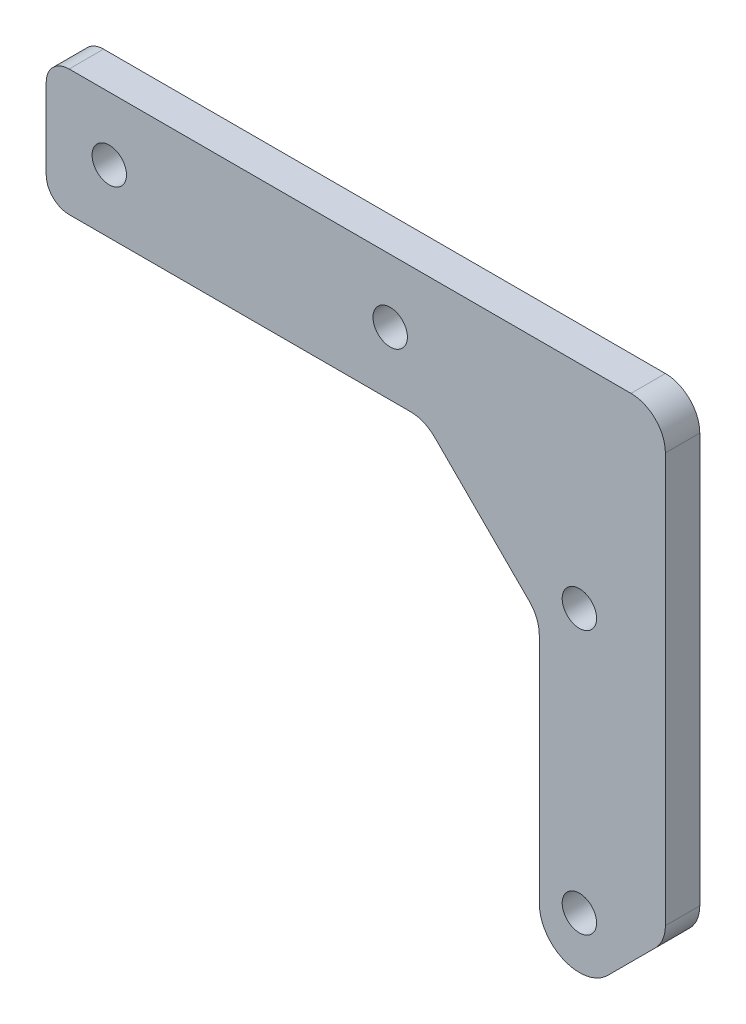
SolidWorks part; units mm, degrees
ref_plane "Спереди" through (0, 0, 0) normal (0, 0, 1) x (1, 0, 0)
ref_plane "Сверху" through (0, 0, 0) normal (0, 1, 0) x (1, 0, 0)
ref_plane "Справа" through (0, 0, 0) normal (1, 0, 0) x (0, 0, -1)
sketch "Эскиз1" plane through (0, 0, 0) normal (0, 0, 1) x (1, 0, 0)
  line L0 (-48.5, 0) -> (5.5, 0) construction
  line L1 (-2, 5.5) -> (-2, -46.5) construction
  line L2 (-48.5, 5.5) -> (-48.5, -5.5)
  line L3 (-48.5, -5.5) -> (-15.5, -5.5)
  line L4 (-5.5, -46.5) -> (5.5, -46.5) construction
  line L5 (-5.5, -15.5) -> (-5.5, -37)
  line L6 (5.5, -34.4497) -> (5.5, 5.5)
  line L7 (5.5, 5.5) -> (-48.5, 5.5)
  line L8 (-15.5, -5.5) -> (-5.5, -15.5)
  line L9 (0, 5.5) -> (0, -46.5) construction
  line L10 (0.4749, -39.4749) -> (5.5, -34.4497)
  line L11 (-5.5, -37) -> (-5.5, -46.5) construction
  line L12 (5.5, -34.4497) -> (5.5, -46.5) construction
  line L13 (-38.5, 5.5) -> (-38.5, -5.5) construction
  arc A0 (-5.5, -37) -> (0.4749, -39.4749) centre (-2, -37) ccw
  circle A4 centre (-18.5, 0) radius 1.5
  circle A5 centre (-43, 0) radius 1.5
  circle A6 centre (-2, -13) radius 1.5
  circle A7 centre (-2, -36) radius 1.5
  dimension "D4" = 11
  dimension "D7" = 13
  dimension "D12" = 3
  dimension "D10" = 45
  dimension "D13" = 24
  dimension "D1" = 11
  dimension "D2" = 43
  dimension "D3" = 52
  dimension "D5" = 10
  dimension "D6" = 45
  dimension "D8" = 3.5
  dimension "D9" = 4.5
  dimension "D11" = 20
  dimension "D14" = 10
  dimension "D16" = 23
extrude "тело" add sketch "Эскиз1" along normal blind 3
fillet "Fillet1" radius 3 4 edges at (5.5, 5.5, 1.5) (5.5, -34.4497, 1.5) (-5.5, -15.5, 1.5) (-15.5, -5.5, 1.5)
chamfer "Фаски под шляпки (левая)" [suppressed] distance 1.5 angle 45
chamfer "Фаски под шляпки (правая)" [suppressed] distance 1.5 angle 45
fillet "Скругление1" radius 2 2 edges at (-48.5, 5.5, 1.5) (-48.5, -5.5, 1.5)
